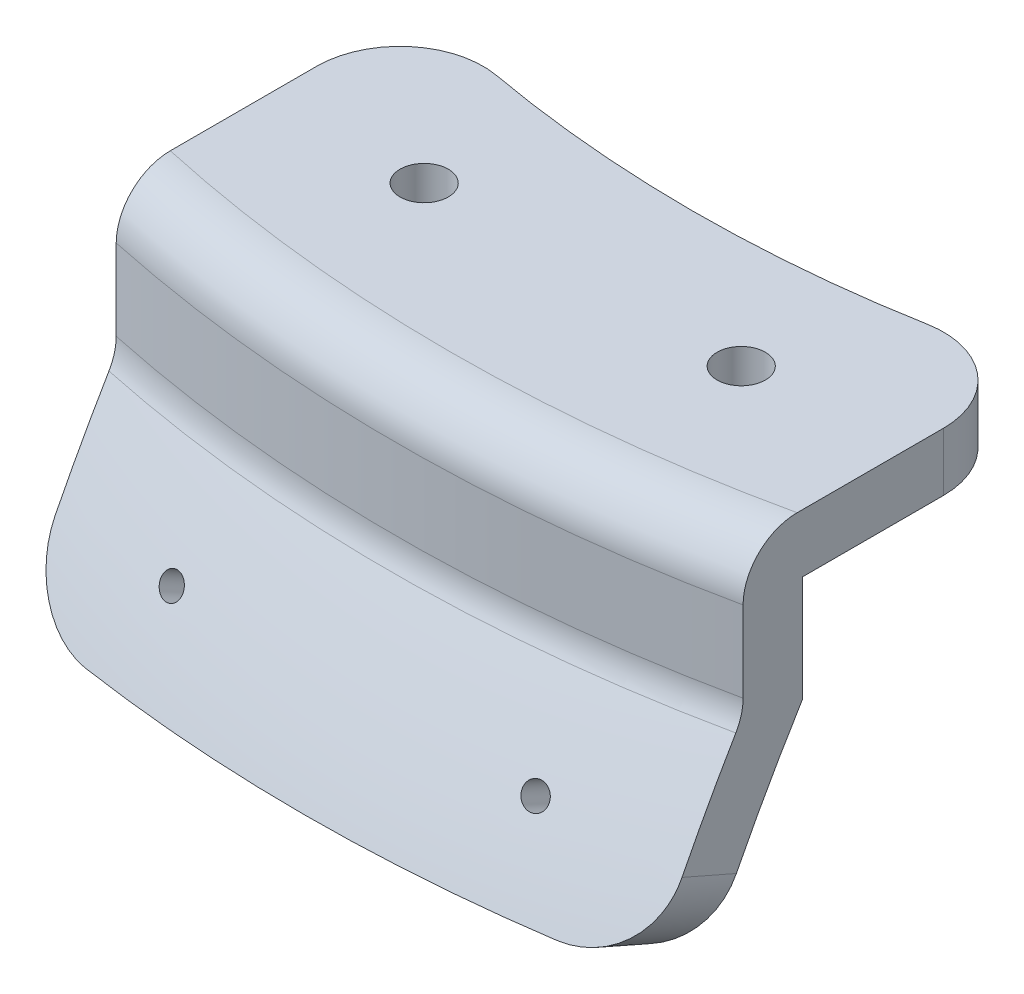
SolidWorks part; units mm, degrees
material "Polyether Polyol"
ref_plane "Front Plane" through (0, 0, 0) normal (0, 0, 1) x (1, 0, 0)
ref_plane "Top Plane" through (0, 0, 0) normal (0, 1, 0) x (1, 0, 0)
ref_plane "Right Plane" through (0, 0, 0) normal (1, 0, 0) x (0, 0, -1)
sketch "Sketch2" plane through (0, 0, 0) normal (1, 0, 0) x (0, 0, -1)
  line L0 (-174.1012, 207.3685) -> (-174.1012, 194.6685) construction
  line L1 (-192.235, 174.9156) -> (-185.8333, 172.084) construction
  line L2 (-181.1012, 214.3685) -> (-181.1012, 196.5948) construction
  line L3 (-181.1012, 214.3685) -> (-145.5262, 214.3685) construction
  line L4 (-145.5262, 214.3685) -> (-145.5262, 207.3685) construction
  line L5 (-145.5262, 207.3685) -> (-174.1012, 207.3685) construction
  line L12 (0, 89.8878) -> (0, 207.3685) construction
  line L13 (-174.1012, 207.3685) -> (-174.1012, 194.6685)
  line L14 (-192.235, 174.9156) -> (-185.8333, 172.084)
  line L15 (-181.1012, 214.3685) -> (-181.1012, 196.5948)
  line L16 (-181.1012, 214.3685) -> (-145.5262, 214.3685)
  line L17 (-145.5262, 214.3685) -> (-145.5262, 207.3685)
  line L18 (-145.5262, 207.3685) -> (-174.1012, 207.3685)
  arc A0 (-174.1012, 194.6685) -> (-185.8333, 172.084) centre (0, 89.8878) ccw construction
  arc A1 (-181.1012, 196.5948) -> (-192.235, 174.9156) centre (0, 89.8878) ccw construction
  arc A4 (-174.1012, 194.6685) -> (-185.8333, 172.084) centre (0, 89.8878) ccw
  arc A5 (-181.1012, 196.5948) -> (-192.235, 174.9156) centre (0, 89.8878) ccw
revolve "Revolve1" add sketch "Sketch2" angle 30 mid plane about L12 other way angle 30
fillet "Fillet1" radius 6.35 2 edges at (0, 196.5948, 181.1012) (0, 214.3685, 181.1012)
sketch "Sketch3" plane through (0, 214.3685, 0) normal (0, -1, 0) x (1, 0, 0)
  circle A2 centre (-19.05, 158.75) radius 3.5719 construction
  circle A3 centre (19.05, 158.75) radius 3.5719 construction
  circle A4 centre (19.05, 158.75) radius 2.9
  circle A5 centre (-19.05, 158.75) radius 2.9
  dimension "D1" = 5.8
extrude "Cut-Extrude1" cut sketch "Sketch3" along normal through all contours A4 | A5 region at (19.05, 214.3685, 158.75) region at (-19.05, 214.3685, 158.75)
sketch "Sketch4" plane through (0, 214.3685, 0) normal (0, 1, 0) x (1, 0, 0)
  line L0 (37.665, -140.5675) -> (45.2289, -168.7967) construction
  line L1 (37.665, -140.5675) -> (-37.665, -140.5675)
  line L2 (37.665, -140.5675) -> (37.665, -192.235)
  line L3 (37.665, -192.235) -> (-37.665, -192.235)
  line L4 (-37.665, -140.5675) -> (-37.665, -192.235)
  line L5 (-37.665, -140.5675) -> (-45.2289, -168.7967) construction
  arc A0 (-37.665, -140.5675) -> (37.665, -140.5675) centre (0, 0) ccw construction
  arc A1 (-49.7541, -185.6848) -> (49.7541, -185.6848) centre (0, 0) ccw construction
extrude "Cut-Extrude2" cut sketch "Sketch4" against normal through all flip side to cut
fillet "Fillet2" radius 10 4 edges at (-37.665, 210.8685, 140.5675) (37.665, 210.8685, 140.5675)
sketch "Sketch5" plane through (0, 0, 0) normal (-1, 0, 0) x (0, 0, 1)
  line L0 (0, 89.8878) -> (181.0525, 182.1386) construction
  line L2 (0, -200000) -> (0, 218797.9879) construction
  arc A0 (185.8333, 172.084) -> (174.1012, 194.6685) centre (0, 89.8878) ccw construction
  dimension "D1" = 63
ref_plane "Plane1" through (0, 71.3612, -36.3604) normal (0, 0.891, -0.454) x (0, 0.454, 0.891)
sketch "Sketch6" plane through (0, 71.3612, -36.3604) normal (0, 0.891, -0.454) x (0, 0.454, 0.891)
  line L0 (216.935, 18.9794) -> (275.7942, 24.1289) construction
  line L2 (216.935, 18.9794) -> (275.7942, 24.1289)
  line L3 (216.935, 18.9794) -> (216.8043, 20.4736)
  line L4 (275.7942, 24.1289) -> (275.6635, 25.6232)
  line L5 (216.8043, 20.4736) -> (275.6635, 25.6232)
  line L6 (40.8082, 0) -> (244.0082, 0) construction
  ellipse E0 centre (88.3777, 0) end of major axis (88.3777, 145.5262) minor radius 129.6648 construction
  dimension "D1" = 5
  dimension "D2" = 1.5
revolve "Cut-Revolve1" cut sketch "Sketch6" angle 360 about L0
mirror "Mirror1" about plane through (0, 0, 0) normal (1, 0, 0) of "Cut-Revolve1"
